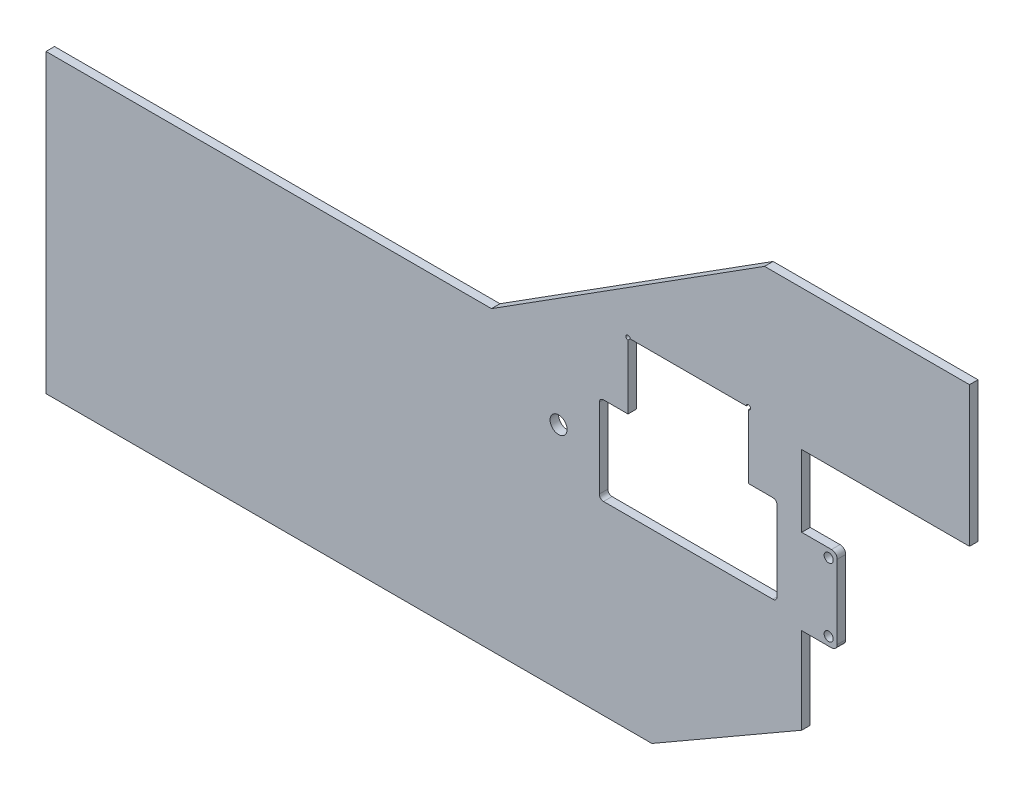
SolidWorks part; units mm, degrees
material "Thornel Mat VMA"
ref_plane "Front Plane" through (0, 0, 0) normal (0, 0, 1) x (1, 0, 0)
ref_plane "Top Plane" through (0, 0, 0) normal (0, 1, 0) x (1, 0, 0)
ref_plane "Right Plane" through (0, 0, 0) normal (1, 0, 0) x (0, 0, -1)
sketch "Sketch1" plane through (0, 0, 0) normal (0, 0, 1) x (1, 0, 0)
  line L1 (-20.4587, 47.6) -> (-183.6375, 47.6)
  line L2 (-20.4587, 47.6) -> (-20.4587, -36.0143)
  line L3 (-20.4587, -36.0143) -> (-183.6375, -36.0143)
  line L4 (-183.6375, 47.6) -> (-183.6375, -36.0143)
extrude "Boss-Extrude1" add sketch "Sketch1" along normal blind 3
sketch "Sketch2" plane through (0, 0, 3) normal (0, 0, 1) x (1, 0, 0)
  circle A0 centre (-24.2887, 24) radius 3
  dimension "D1" = 6
extrude "Cut-Extrude1" cut sketch "Sketch2" against normal blind 70
sketch "Sketch3" plane through (0, 0, 3) normal (0, 0, 1) x (1, 0, 0)
  line L4 (-20.4587, -36.0143) -> (-20.4587, 47.6)
  line L5 (-20.4587, 47.6) -> (-183.6375, 47.6)
  line L6 (-183.6375, 47.6) -> (-183.6375, -36.0143)
  line L7 (-183.6375, -36.0143) -> (-20.4587, -36.0143)
  line L8 (-20.4587, -36.0143) -> (-20.4587, 47.6)
  line L9 (-20.4587, 47.6) -> (-47.9302, 47.6)
  line L10 (-183.6375, 47.6) -> (-183.6375, -36.0143)
  line L11 (-183.6375, -36.0143) -> (-20.4587, -36.0143)
  line L13 (48.2808, 108.6033) -> (-47.9302, 47.6)
  line L14 (-47.9302, 47.6) -> (-204.873, 47.6)
  line L15 (-204.873, 47.6) -> (-204.873, -56.8219)
  line L16 (-204.873, -56.8219) -> (8.5855, -56.8219)
  line L17 (8.5855, -56.8219) -> (61.3713, -26.3865)
  line L18 (61.3713, -26.3865) -> (61.3713, 4)
  line L19 (61.3713, 4) -> (71.8713, 4)
  line L20 (73.8713, 6) -> (73.8713, 32)
  line L21 (71.8713, 34) -> (61.3713, 34)
  line L22 (61.3713, 34) -> (61.3713, 59.2602)
  line L23 (61.3713, 59.2602) -> (120.4754, 59.2602)
  line L24 (120.4754, 59.2602) -> (120.4754, 108.6033)
  line L25 (120.4754, 108.6033) -> (48.2808, 108.6033)
  line L26 (48.2808, 108.6033) -> (-47.9302, 47.6)
  line L27 (-183.6375, 47.6) -> (-204.873, 47.6)
  line L28 (-204.873, 47.6) -> (-204.873, -56.8219)
  line L29 (-204.873, -56.8219) -> (8.5855, -56.8219)
  line L30 (8.5855, -56.8219) -> (61.3713, -26.3865)
  line L31 (61.3713, -26.3865) -> (61.3713, 4)
  line L32 (61.3713, 4) -> (71.8713, 4)
  line L33 (73.8713, 6) -> (73.8713, 32)
  line L34 (71.8713, 34) -> (61.3713, 34)
  line L35 (61.3713, 34) -> (61.3713, 59.2602)
  line L36 (61.3713, 59.2602) -> (120.4754, 59.2602)
  line L37 (120.4754, 59.2602) -> (120.4754, 108.6033)
  line L38 (120.4754, 108.6033) -> (48.2808, 108.6033)
  circle A0 centre (70.8713, 31) radius 1.6 construction
  circle A1 centre (70.8713, 7) radius 1.6 construction
  arc A2 (71.8713, 4) -> (73.8713, 6) centre (71.8713, 6) ccw
  arc A3 (73.8713, 32) -> (71.8713, 34) centre (71.8713, 32) ccw
  arc A4 (71.8713, 4) -> (73.8713, 6) centre (71.8713, 6) ccw
  arc A5 (73.8713, 32) -> (71.8713, 34) centre (71.8713, 32) ccw
  circle A6 centre (70.8713, 31) radius 1.6
  circle A7 centre (70.8713, 7) radius 1.6
  dimension "D1" = 0
  dimension "D2" = 0
extrude "Boss-Extrude2" add sketch "Sketch3" against normal blind 3
sketch "Sketch4" plane through (0, 0, 3) normal (0, 0, 1) x (1, 0, 0)
  line L0 (0.1713, 62.05) -> (0.1713, 39.5) construction
  line L1 (-8.4587, 39.5) -> (0.1713, 39.5) construction
  line L2 (-9.9587, 10) -> (-9.9587, 38) construction
  line L3 (-8.4587, 8.5) -> (51.2013, 8.5) construction
  line L4 (52.7013, 10) -> (52.7013, 38) construction
  line L5 (42.5713, 39.5) -> (51.2013, 39.5) construction
  line L6 (42.5713, 62.05) -> (42.5713, 39.5) construction
  line L7 (41.8213, 62.8) -> (0.9213, 62.8) construction
  line L8 (0.1713, 62.05) -> (0.1713, 39.5)
  line L9 (-8.4587, 39.5) -> (0.1713, 39.5)
  line L10 (-9.9587, 10) -> (-9.9587, 38)
  line L11 (-8.4587, 8.5) -> (51.2013, 8.5)
  line L12 (52.7013, 10) -> (52.7013, 38)
  line L13 (42.5713, 39.5) -> (51.2013, 39.5)
  line L14 (42.5713, 62.05) -> (42.5713, 39.5)
  line L15 (41.8213, 62.8) -> (0.9213, 62.8)
  arc A0 (0.9213, 62.8) -> (0.1713, 62.05) centre (0.1713, 62.8) ccw construction
  arc A1 (-8.4587, 39.5) -> (-9.9587, 38) centre (-8.4587, 38) ccw construction
  arc A2 (-9.9587, 10) -> (-8.4587, 8.5) centre (-8.4587, 10) ccw construction
  arc A3 (51.2013, 8.5) -> (52.7013, 10) centre (51.2013, 10) ccw construction
  arc A4 (52.7013, 38) -> (51.2013, 39.5) centre (51.2013, 38) ccw construction
  arc A5 (42.5713, 62.05) -> (41.8213, 62.8) centre (42.5713, 62.8) ccw construction
  arc A6 (0.9213, 62.8) -> (0.1713, 62.05) centre (0.1713, 62.8) ccw
  arc A7 (-8.4587, 39.5) -> (-9.9587, 38) centre (-8.4587, 38) ccw
  arc A8 (-9.9587, 10) -> (-8.4587, 8.5) centre (-8.4587, 10) ccw
  arc A9 (51.2013, 8.5) -> (52.7013, 10) centre (51.2013, 10) ccw
  arc A10 (52.7013, 38) -> (51.2013, 39.5) centre (51.2013, 38) ccw
  arc A11 (42.5713, 62.05) -> (41.8213, 62.8) centre (42.5713, 62.8) ccw
extrude "Cut-Extrude2" cut sketch "Sketch4" against normal blind 10
